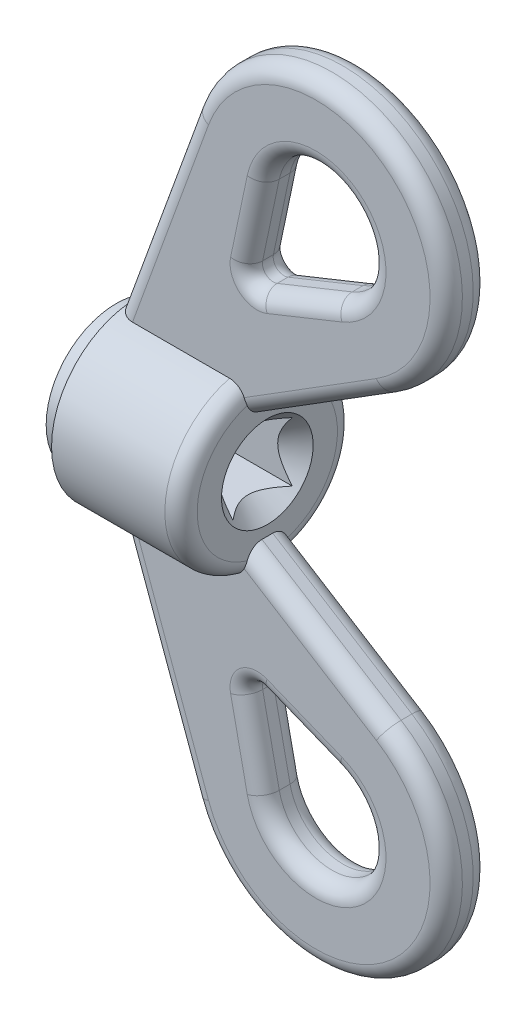
SolidWorks part; units mm, degrees
ref_plane "Alzado" through (0, 0, 0) normal (0, 0, 1) x (1, 0, 0)
ref_plane "Planta" through (0, 0, 0) normal (0, 1, 0) x (1, 0, 0)
ref_plane "Vista lateral" through (0, 0, 0) normal (1, 0, 0) x (0, 0, -1)
sketch "Sketch1" plane through (0, 0, 0) normal (0, 0, 1) x (1, 0, 0)
  line L0 (-7.4306, 0) -> (19.6409, 0) construction
  line L9 (0, 0) -> (0, 76.4795) construction
  line L11 (0, 6.5) -> (2, 6.5)
  line L12 (0, 6.5) -> (0, 4.25)
  line L15 (2, 8) -> (14, 8)
  line L16 (2, 8) -> (2, 6.5)
  line L17 (3.5, 0) -> (14, 0)
  line L18 (14, 8) -> (14, 0)
  line L21 (0, 4.25) -> (3.5, 4.25)
  line L22 (3.5, 0) -> (3.5, 4.25)
  point P16 (0, 0)
  dimension "D1" = 2
  dimension "D2" = 6.5
  dimension "D3" = 4.25
  dimension "D4" = 8
  dimension "D5" = 12
  dimension "D6" = 3.5
revolve "Revolve1" add sketch "Sketch1" angle 360 about L0
sketch "Sketch2" plane through (0, 0, 0) normal (0, 0, 1) x (1, 0, 0)
  line L0 (0, 0) -> (39.467, 0) construction
  line L1 (2, 8) -> (9.1457, 27.6326) construction
  line L2 (15.607, 24.5288) -> (14.0672, 17.2058)
  line L3 (22.3628, 18.86) -> (15.4184, 16.072)
  line L4 (2, 0) -> (2, 37.5333) construction
  line L5 (2, 8) -> (2, -8) construction
  line L6 (20.5, 23.5) -> (2, 1.4526) construction
  line L7 (14, 8) -> (2, 8) construction
  line L8 (9.1457, 27.6326) -> (2, 8)
  line L9 (26.903, 13.253) -> (14, 5.1903)
  line L10 (14, -8) -> (14, 8) construction
  line L15 (2, 8) -> (2, 5.1903)
  line L16 (2, 5.1903) -> (14, 5.1903)
  arc A0 (22.3628, 18.86) -> (15.607, 24.5288) centre (20.5, 23.5) ccw
  arc A1 (14.0672, 17.2058) -> (15.4184, 16.072) centre (15.0459, 17) ccw
  arc A2 (26.903, 13.253) -> (9.1457, 27.6326) centre (20.5, 23.5) ccw
  point P19 (0, 0)
  point P20 (0, 0)
  point P22 (0, 0)
  point P26 (0, 0)
  dimension "D1" = 10
  dimension "D4" = 2
  dimension "D2" = 23.5
  dimension "D3" = 18.5
  dimension "D5" = 17
  dimension "D6" = 40
  dimension "D7" = 20
  dimension "D8" = 38
extrude "Boss-Extrude7" add sketch "Sketch2" along normal blind 2 and the other way blind 2
fillet "Fillet1" radius 1.5 14 edges at (14.4031, 16.234, 2) (18.8906, 17.466, 2) (14.8371, 20.8673, 2) (23.7139, 27.3302, 2) (23.7139, 27.3302, -2) (14.4031, 16.234, -2) (18.8906, 17.466, -2) (14.8371, 20.8673, -2) (5.5728, 17.8163, -2) (20.4515, 9.2217, -2) (28.1041, 32.8903, -2) (5.5728, 17.8163, 2) (20.4515, 9.2217, 2) (28.1041, 32.8903, 2)
fillet "Fillet2" radius 1.5 1 edges at (14, -8, 0)
mirror "Mirror1" about plane through (0, 0, 0) normal (0, 1, 0) of "Fillet1", "Boss-Extrude7"
sketch "Sketch8" plane through (14, 0, 0) normal (1, 0, 0) x (0, 0, -1)
  line L1 (-2.75, -2.75) -> (2.75, -2.75)
  line L2 (-2.75, -2.75) -> (-2.75, 2.75)
  line L3 (-2.75, 2.75) -> (2.75, 2.75)
  line L4 (2.75, -2.75) -> (2.75, 2.75)
  line L5 (-2.75, -2.75) -> (2.75, 2.75) construction
  line L6 (-2.75, 2.75) -> (2.75, -2.75) construction
  circle A0 centre (0, 0) radius 3.8891
  point P0 (0, 0)
  dimension "D1" = 5.5
  dimension "D2" = 5.5
extrude "Cut-Extrude2" cut sketch "Sketch8" against normal through all contours L1 L4 L3 L2 region at (14, 0, 0)
sketch "Sketch11" plane through (0, 0, 0) normal (0, 1, 0) x (1, 0, 0)
  line L1 (14, 2.75) -> (12.2124, 2.75)
  line L2 (12.2124, 2.75) -> (14, 4.25)
  line L3 (14, 4.25) -> (14, 2.75)
  line L4 (3.5, 2.75) -> (14, 2.75) construction
  line L5 (14, -2.75) -> (14, 2.75) construction
  line L6 (0, 0) -> (19.5702, 0) construction
  dimension "D1" = 40
  dimension "D2" = 4.25
revolve "Cut-Revolve2" cut sketch "Sketch11" angle 360 about L6
